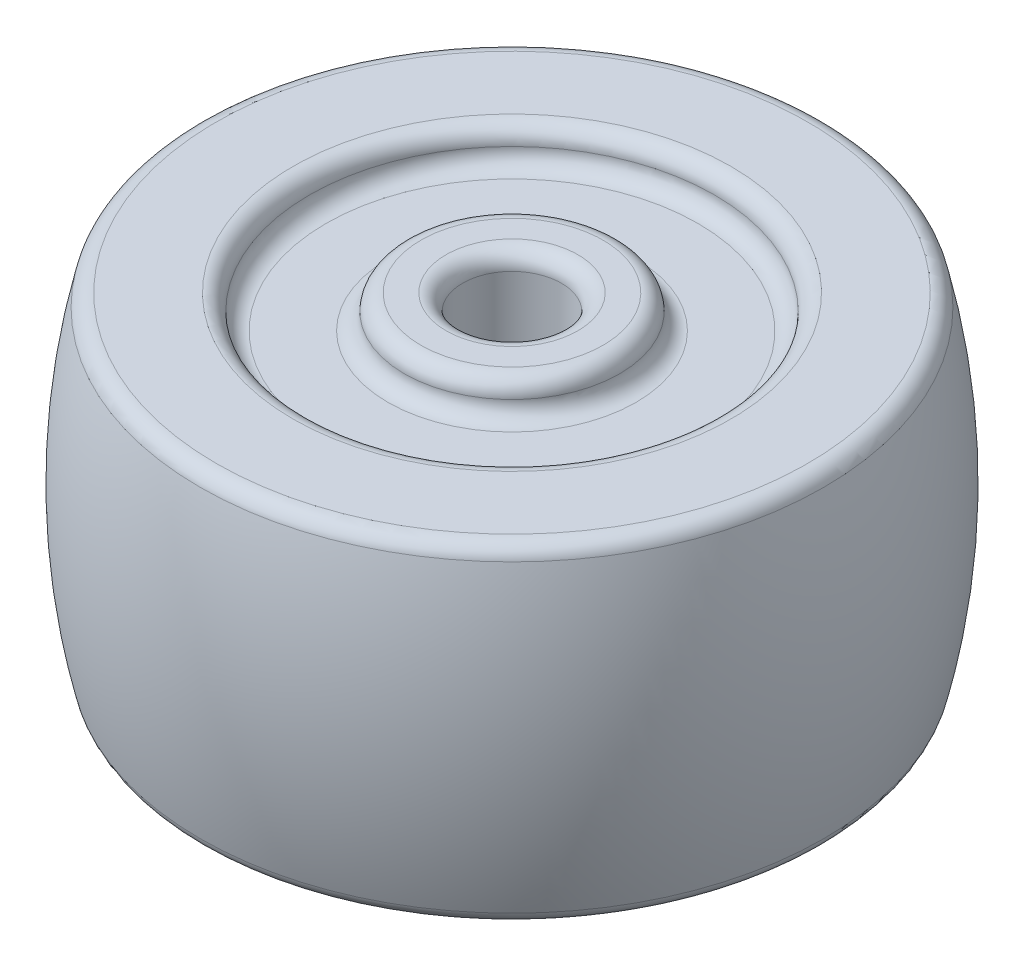
SolidWorks part; units mm, degrees
ref_plane "前视基准面" through (0, 0, 0) normal (0, 0, 1) x (1, 0, 0)
ref_plane "上视基准面" through (0, 0, 0) normal (0, 1, 0) x (1, 0, 0)
ref_plane "右视基准面" through (0, 0, 0) normal (1, 0, 0) x (0, 0, -1)
sketch "草图1" plane through (0, 0, 0) normal (0, 0, 1) x (1, 0, 0)
  line L0 (0, 10) -> (0, -10)
  line L1 (-3, -10) -> (-6.5285, -10)
  line L3 (-3, 10) -> (-6.5285, 10)
  line L5 (-3, 1.6017) -> (-18.7298, 10) construction
  line L6 (-3, -1.6017) -> (-18.7298, -10) construction
  line L7 (-3, 10) -> (-3, -10)
  line L8 (-12.2832, 10) -> (-12.2832, 8)
  line L9 (-12.2832, 8) -> (-6.5285, 8)
  line L10 (-6.5285, 8) -> (-6.5285, 10)
  line L11 (-12.2832, -10) -> (-12.2832, -8)
  line L12 (-12.2832, -8) -> (-6.5285, -8)
  line L13 (-6.5285, -8) -> (-6.5285, -10)
  line L14 (-12.2832, 10) -> (-18.7298, 10)
  line L15 (-12.2832, -10) -> (-18.7298, -10)
  arc A0 (-18.7298, 10) -> (-18.7298, -10) centre (20, 0) ccw
  point P0 (0, 0)
  point P7 (-20, 0)
  dimension "D2" = 40
  dimension "D1" = 20
  dimension "D3" = 20
  dimension "D4" = 3
  dimension "D5" = 2
  dimension "D6" = 2
revolve "旋转1" add sketch "草图1" angle 360 about L0 region at (-11.4348, 0, 0)
fillet "圆角1" radius 1 11 edges at (0, -8, 12.2832) (0, 8, 12.2832) (0, 8, 6.5285) (0, -10, 3) (0, -10, 6.5285) (0, -10, 12.2832) (0, -10, 18.7298) (0, 10, 3) (0, 10, 6.5285) (0, 10, 12.2832) (0, 10, 18.7298)
